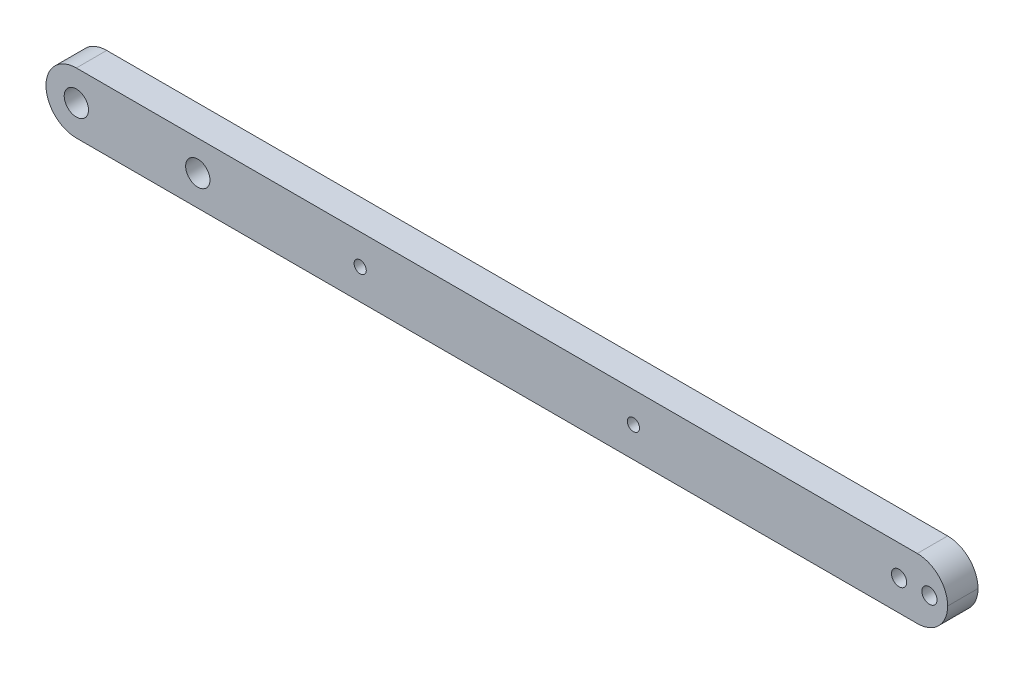
SolidWorks part; units mm, degrees
material "AISI 316 Barre d'acier inoxydable recuit (SS)"
ref_plane "Plan de face" through (0, 0, 0) normal (0, 0, 1) x (1, 0, 0)
ref_plane "Plan de dessus" through (0, 0, 0) normal (0, 1, 0) x (1, 0, 0)
ref_plane "Plan de droite" through (0, 0, 0) normal (1, 0, 0) x (0, 0, -1)
sketch "Esquisse1" plane through (0, 0, 0) normal (0, 0, 1) x (1, 0, 0)
  line L0 (0, 10) -> (297, 10) construction
  line L1 (0, 20) -> (297, 20)
  line L2 (0, 20) -> (0, 0)
  line L3 (0, 0) -> (297, 0)
  line L4 (297, 20) -> (297, 0)
  line L5 (148.5, 20) -> (148.5, 0) construction
  circle A0 centre (10, 10) radius 4
  circle A1 centre (50, 10) radius 4
  circle A2 centre (281, 10) radius 2.5
  circle A3 centre (291, 10) radius 2.5
  circle A4 centre (103.5, 10) radius 2
  circle A5 centre (193.5, 10) radius 2
  dimension "D3" = 8
  dimension "D4" = 40
  dimension "D7" = 5
  dimension "D9" = 90
  dimension "D10" = 4
  dimension "D11" = 90
  dimension "D1" = 20
  dimension "D2" = 297
  dimension "D5" = 10
  dimension "D6" = 10
  dimension "D8" = 6
extrude "Boss.-Extru.1" add sketch "Esquisse1" along normal blind 10
fillet "Congé1" radius 10 4 edges at (0, 0, 5) (0, 20, 5) (297, 0, 5) (297, 20, 5)
